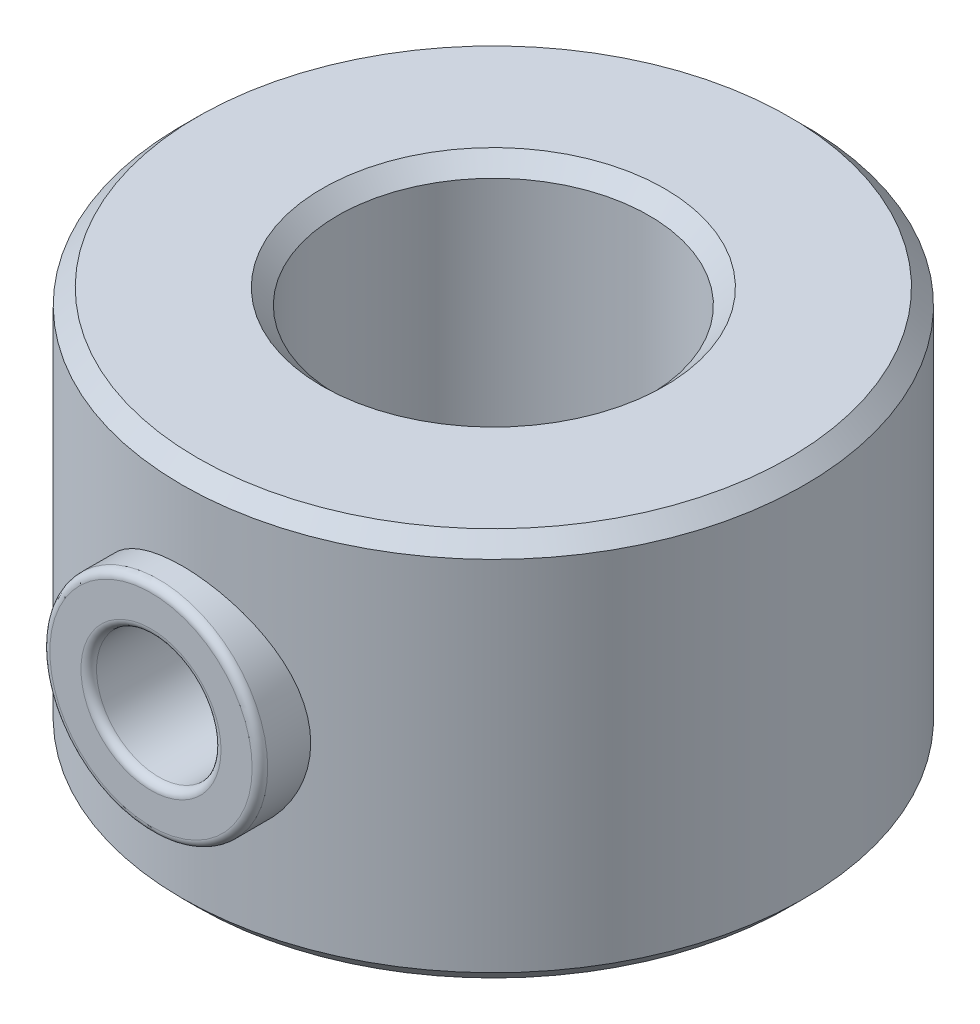
SolidWorks part; units mm, degrees
material "Stainless Steel (ferritic)"
ref_plane "Front Plane" through (0, 0, 0) normal (0, 0, 1) x (1, 0, 0)
ref_plane "Top Plane" through (0, 0, 0) normal (0, 1, 0) x (1, 0, 0)
ref_plane "Right Plane" through (0, 0, 0) normal (1, 0, 0) x (0, 0, -1)
sketch "Sketch1" plane through (0, 0, 0) normal (0, 1, 0) x (1, 0, 0)
  circle A0 centre (0, 0) radius 2
  circle A1 centre (0, 0) radius 4
  dimension "D1" = 4
  dimension "D2" = 8
extrude "Boss-Extrude1" add sketch "Sketch1" along normal blind 5
sketch "Sketch2" plane through (0, 0, 0) normal (0, 0, 1) x (1, 0, 0)
  line L0 (-4, 0) -> (4, 0) construction
  circle A0 centre (0, 2.5) radius 1.4
  dimension "D2" = 2.8
  dimension "D1" = 2.5
extrude "Boss-Extrude2" add sketch "Sketch2" along normal blind 4.4
sketch "Sketch3" plane through (0, 5, 0) normal (0, 1, 0) x (1, 0, 0)
  circle A0 centre (0, 0) radius 2
extrude "Cut-Extrude1" cut sketch "Sketch3" against normal blind 4.2
sketch "Sketch4" plane through (0, 0, 4.4) normal (0, 0, 1) x (1, 0, 0)
  circle A0 centre (0, 2.5) radius 0.8
  dimension "D1" = 1.6
extrude "Cut-Extrude2" cut sketch "Sketch4" against normal blind 4.2
fillet "Fillet1" radius 0.1 2 edges at (0.8, 2.5, 4.4) (1.4, 2.5, 4.4)
chamfer "Chamfer1" distance 0.2 angle 45 4 edges at (0, 0, 2) (0, 0, 4) (0, 5, 2) (0, 5, 4)
